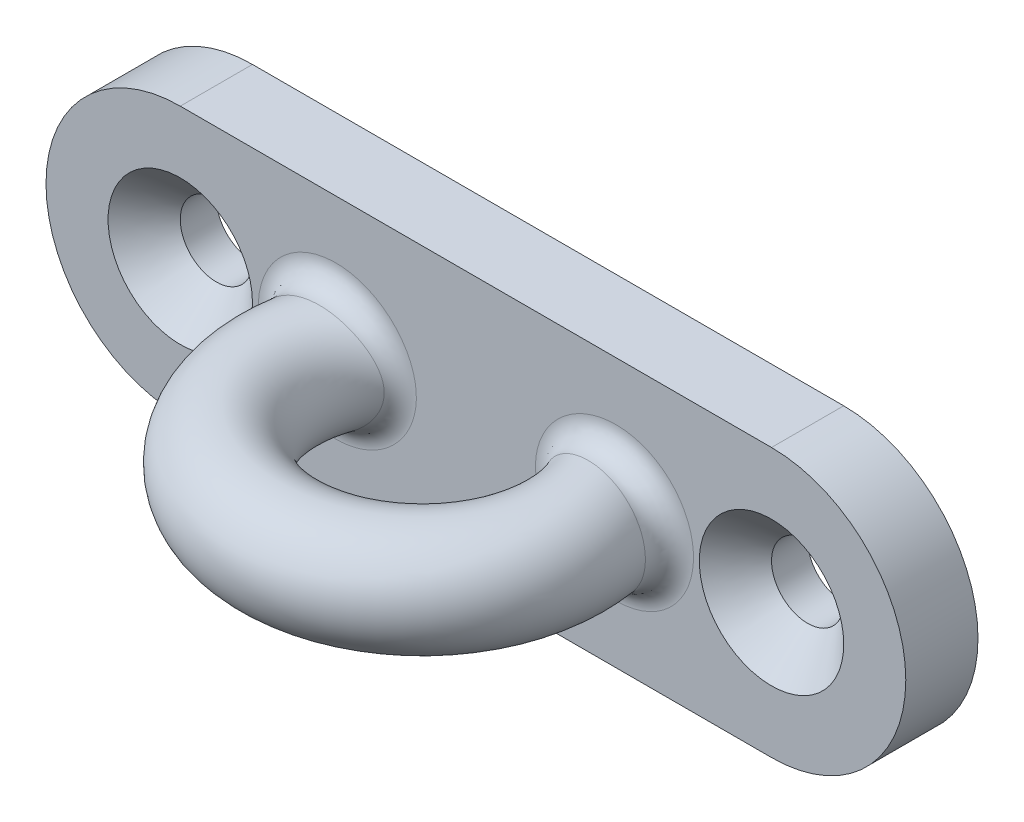
SolidWorks part; units mm, degrees
material "Cast Stainless Steel"
ref_plane "Front Plane" through (0, 0, 0) normal (0, 0, 1) x (1, 0, 0)
ref_plane "Top Plane" through (0, 0, 0) normal (0, 1, 0) x (1, 0, 0)
ref_plane "Right Plane" through (0, 0, 0) normal (1, 0, 0) x (0, 0, -1)
sketch "Sketch1" plane through (0, 0, 0) normal (0, 0, 1) x (1, 0, 0)
  line L0 (0, 11.9) -> (52.4, 11.9)
  line L1 (52.4, -11.9) -> (0, -11.9)
  line L2 (26.2, -11.9) -> (26.2, 11.9) construction
  line L3 (-11.9, 11.9) -> (64.3, 11.9) construction
  line L4 (-11.9, 11.9) -> (-11.9, -11.9) construction
  line L5 (-11.9, -11.9) -> (64.3, -11.9) construction
  line L6 (64.3, 11.9) -> (64.3, -11.9) construction
  line L7 (0, 0) -> (52.4, 0) construction
  circle A0 centre (0, 0) radius 3.2
  circle A1 centre (0, 0) radius 11.9
  circle A2 centre (52.4, 0) radius 3.2
  circle A3 centre (52.4, 0) radius 11.9
  point P17 (26.2, 0)
  dimension "D2" = 76.2
  dimension "D3" = 6.4
  dimension "D1" = 52.4
extrude "Boss-Extrude1" add sketch "Sketch1" along normal blind 6.4 contours A3 L0 A1 L1 | A3 A2 | A1 A0 region at (26.2, 0, 0) region at (8.1766, 8.1766, 0) region at (60.5766, 8.1766, 0)
chamfer "Chamfer1" distance 3.2 angle 45 2 edges at (3.2, 0, 6.4) (55.6, 0, 6.4)
sketch "Sketch3" plane through (0, 0, 0) normal (0, 1, 0) x (1, 0, 0)
  line L0 (37.3881, -19.1) -> (-3.2366, -19.1) construction
  line L1 (52.4, -6.4) -> (0, -6.4) construction
  line L2 (0, 0) -> (52.4, 0) construction
  line L3 (26.2, -11.15) -> (26.2, 0) construction
  line L4 (26.2, 11.4344) -> (26.2, -39.3465) construction
  circle A1 centre (26.2, -11.15) radius 7.95
  circle A2 centre (26.2, -11.15) radius 17.48
  circle A3 centre (26.2, -11.15) radius 12.715 construction
  dimension "D1" = 15.9
  dimension "D2" = 12.7
  dimension "D3" = 9.53
  dimension "D4" = 25.43
ref_plane "Plane1" through (0, 0, 11.15) normal (0, 0, 1) x (1, 0, 0)
sketch "Sketch4" plane through (0, 0, 11.15) normal (0, 0, 1) x (1, 0, 0)
  line L3 (38.915, 0) -> (13.485, 0) construction
  line L4 (38.915, 0) -> (13.485, 0) construction
  line L5 (26.2, 24.5441) -> (26.2, -24.5441) construction
  circle A0 centre (38.915, 0) radius 4.765
  point P7 (26.2, 0)
  dimension "D1" = 9.53
revolve "Revolve6" add sketch "Sketch4" angle 219 about L5 other way angle 38
fillet "Fillet1" radius 2 2 edges at (42.4656, 2.1937, 6.4) (18.8559, 2.6373, 6.4)
